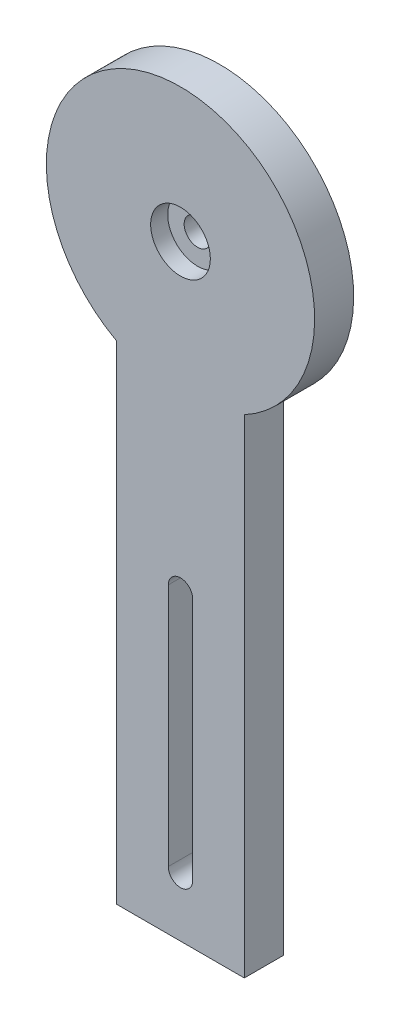
SolidWorks part; units mm, degrees
ref_plane "Piano frontale" through (0, 0, 0) normal (0, 0, 1) x (1, 0, 0)
ref_plane "Piano superiore" through (0, 0, 0) normal (0, 1, 0) x (1, 0, 0)
ref_plane "Piano destro" through (0, 0, 0) normal (1, 0, 0) x (0, 0, -1)
sketch "Schizzo1" plane through (0, 0, 0) normal (0, 0, 1) x (1, 0, 0)
  line L0 (0, 0) -> (0, 100)
  line L1 (0, 0) -> (26.16, 0)
  line L2 (26.16, 0) -> (26.16, 100)
  line L6 (0, 50) -> (13.08, 50) construction
  arc A1 (26.16, 100) -> (0, 100) centre (13.08, 124.1902) ccw
  dimension "D1" = 100
  dimension "D3" = 55
  dimension "D2" = 100
  dimension "D4" = 26.16
extrude "Estrusione-Estrusione1" add sketch "Schizzo1" along normal mid plane 8
sketch "Schizzo2" plane through (0, 0, 4) normal (0, 0, 1) x (1, 0, 0)
  line L0 (0, 50) -> (26.16, 50) construction
  line L1 (0, 100) -> (0, 0) construction
  line L2 (26.16, 0) -> (26.16, 100) construction
  line L3 (13.08, 0) -> (13.08, 99.1276) construction
  line L7 (0, 0) -> (26.16, 0) construction
  line L8 (13.08, 12) -> (13.08, 62) construction
  line L9 (10.58, 12) -> (10.58, 62)
  line L10 (15.58, 12) -> (15.58, 62)
  arc A3 (10.58, 12) -> (15.58, 12) centre (13.08, 12) ccw
  arc A4 (15.58, 62) -> (10.58, 62) centre (13.08, 62) ccw
  point P12 (13.08, 37)
  dimension "D1" = 2.5
  dimension "D3" = 62
  dimension "D2" = 12
extrude "Taglio-Estrusione1" cut sketch "Schizzo2" against normal through all
sketch "Schizzo11" plane through (0, 0, 4) normal (0, 0, 1) x (1, 0, 0)
  arc A0 (26.16, 100) -> (0, 100) centre (13.08, 124.1902) ccw construction
  arc A1 (26.16, 100) -> (0, 100) centre (13.08, 124.1902) ccw construction
hole_wizard "Foro lamato per Bullone M5 a testa esagonale-1" positions "Schizzo12" profile "Schizzo13" counterbore size "M5" standard "ISO" end condition through all
sketch "Schizzo12" plane through (0, 0, 4) normal (0, 0, 1) x (1, 0, 0)
  point P0 (13.08, 124.1902)
sketch "Schizzo13" plane through (13.08, 124.1902, 4) normal (1, 0, 0) x (0, -1, 0)
  line L0 (0, 0) -> (0, 8)
  line L1 (0, 8) -> (2.75, 8)
  line L3 (2.75, 8) -> (2.75, 3.5)
  line L4 (2.75, 3.5) -> (6.119, 3.5)
  line L5 (6.119, 3.5) -> (6.119, 0)
  line L7 (6.119, 0) -> (0, 0)
  line L11 (0, -6.35) -> (0, 107.95) construction
  dimension "Thru Hole Dia." = 5.5
  dimension "Thru Hole Depth" = 8
  dimension "C'Bore Dia." = 12.238
  dimension "C'Bore Depth" = 3.5
